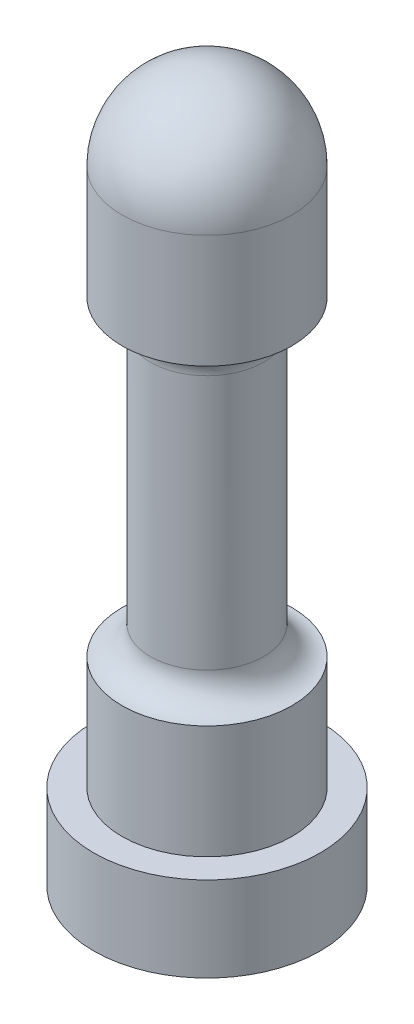
SolidWorks part; units mm, degrees
ref_plane "Front Plane" through (0, 0, 0) normal (0, 0, 1) x (1, 0, 0)
ref_plane "Top Plane" through (0, 0, 0) normal (0, 1, 0) x (1, 0, 0)
ref_plane "Right Plane" through (0, 0, 0) normal (1, 0, 0) x (0, 0, -1)
sketch "Sketch1" plane through (0, 0, 0) normal (0, 0, 1) x (1, 0, 0)
  line L0 (0, 0) -> (0, 25)
  line L1 (0, -55) -> (0, 55) construction
  line L2 (0, 0) -> (4, 0)
  line L3 (4, 0) -> (4, 3)
  line L4 (4, 3) -> (3, 3)
  line L5 (3, 3) -> (3, 7)
  line L6 (3, 7) -> (2, 7)
  line L7 (2, 7) -> (2, 18)
  line L8 (2, 18) -> (3, 18)
  line L9 (3, 18) -> (3, 25)
  line L10 (3, 25) -> (0, 25)
  point P5 (-21.832, 10.7895)
  dimension "D2" = 3
  dimension "D3" = 4
  dimension "D4" = 4
  dimension "D5" = 11
  dimension "D6" = 3
  dimension "D7" = 1
  dimension "D8" = 1
  dimension "D9" = 7
revolve "Revolve1" add sketch "Sketch1" angle 360 about L0
fillet "Fillet1" radius 3 1 edges at (0, 25, -3)
fillet "Fillet2" radius 1 2 edges at (0, 7, -2) (0, 18, -2)
sketch "Sketch2" plane through (0, 0, 0) normal (0, 0, 1) x (1, 0, 0)
  line L0 (0, 2.8255) -> (0, 0)
  line L1 (0, 0) -> (2.8255, 0)
  arc A0 (2.8255, 0) -> (0, 2.8255) centre (0, 0) ccw
revolve "Cut-Revolve1" cut sketch "Sketch2" angle 360 about L0
